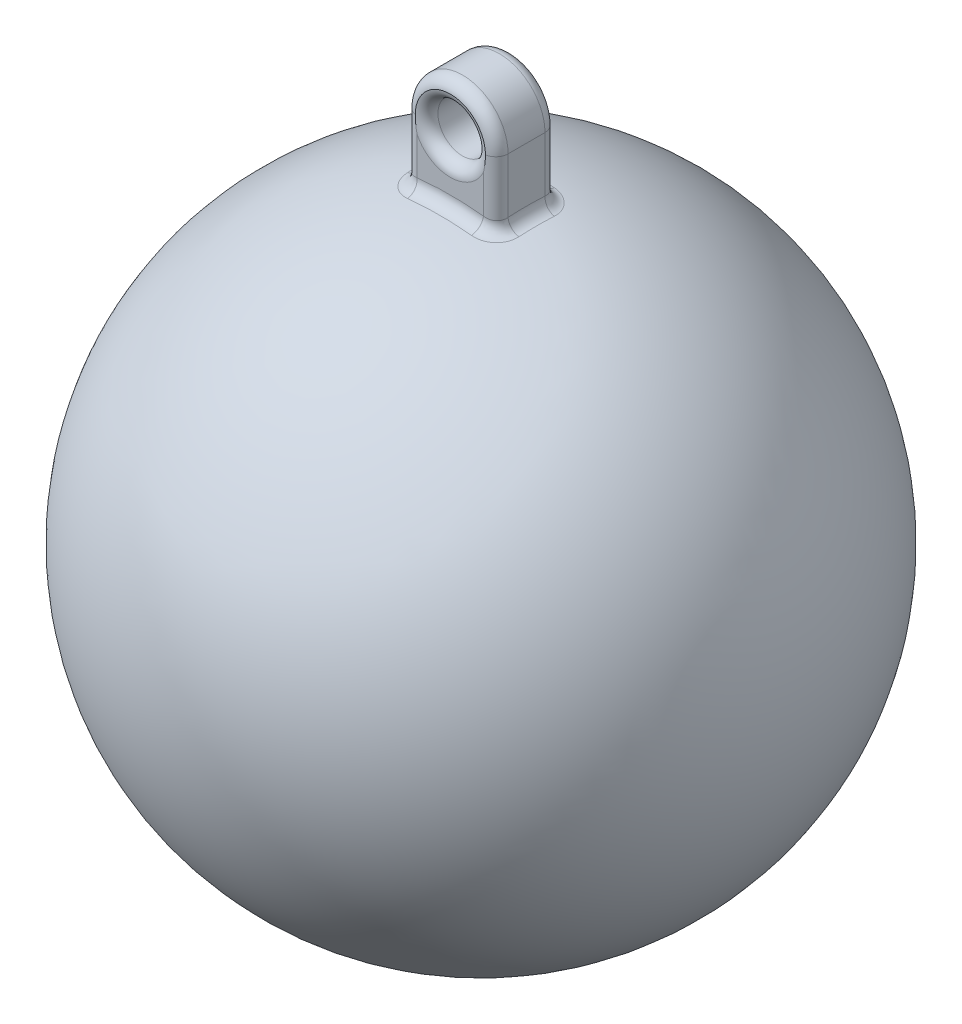
SolidWorks part; units mm, degrees
ref_plane "Front Plane" through (0, 0, 0) normal (0, 0, 1) x (1, 0, 0)
ref_plane "Top Plane" through (0, 0, 0) normal (0, 1, 0) x (1, 0, 0)
ref_plane "Right Plane" through (0, 0, 0) normal (1, 0, 0) x (0, 0, -1)
sketch "Sketch1" plane through (0, 0, 0) normal (0, 1, 0) x (1, 0, 0)
  line L0 (25, 0) -> (-25, 0)
  arc A0 (-25, 0) -> (25, 0) centre (0, 0) ccw
  dimension "D1" = 25
revolve "Revolve1" add sketch "Sketch1" angle 360 about L0
sketch "Sketch2" plane through (0, 0, 0) normal (0, 0, 1) x (1, 0, 0)
  line L0 (0, 0) -> (0, 32.771) construction
  line L2 (-3.7, 30) -> (3.7, 30) construction
  line L3 (-3.7, 30) -> (-3.7, 20)
  line L4 (-3.7, 20) -> (3.7, 20)
  line L5 (3.7, 30) -> (3.7, 20)
  arc A0 (3.7, 30) -> (-3.7, 30) centre (0, 30) ccw
  circle A1 centre (0, 30) radius 2
  dimension "D1" = 3.7
  dimension "D2" = 20
  dimension "D3" = 10
extrude "Boss-Extrude1" add sketch "Sketch2" along normal mid plane 5
fillet "Fillet1" radius 1 12 edges at (-3.7, 24.7247, 0) (3.7, 24.7247, 0) (2, 30, -2.5) (0, 33.7, -2.5) (-3.7, 27.299, -2.5) (0, 24.8747, -2.5) (3.7, 27.299, -2.5) (2, 30, 2.5) (-3.7, 27.299, 2.5) (0, 33.7, 2.5) (3.7, 27.299, 2.5) (0, 24.8747, 2.5)
